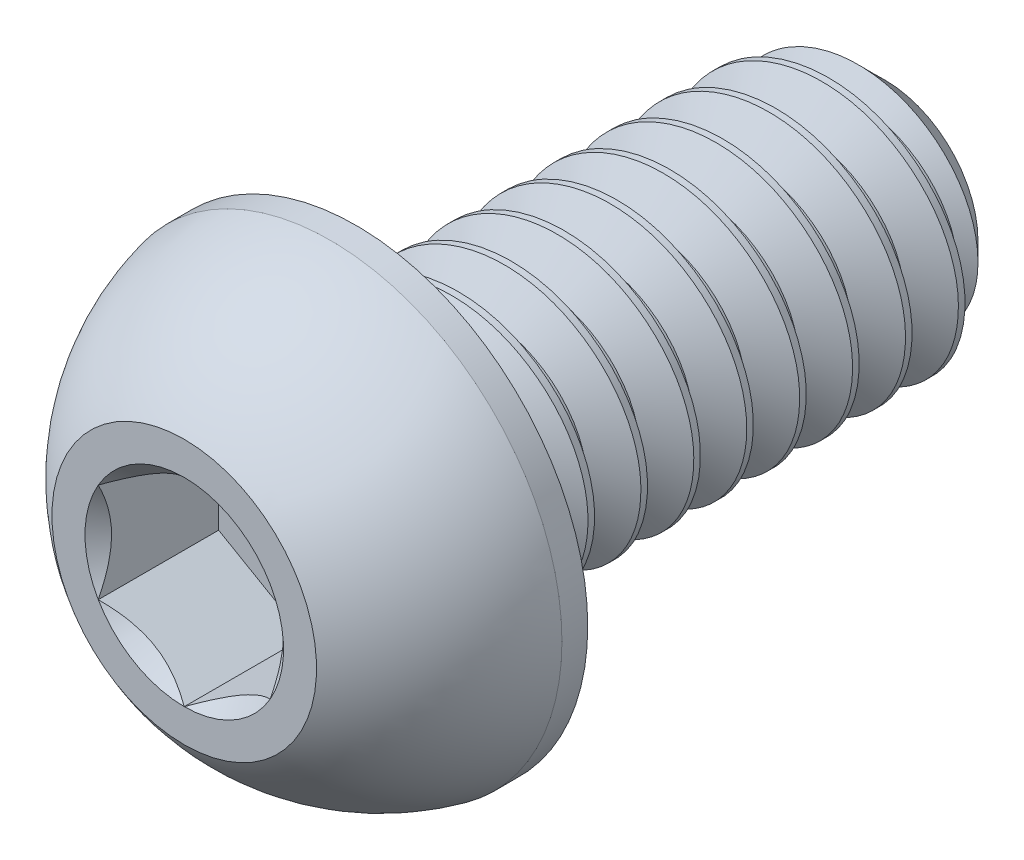
SolidWorks part; units mm, degrees
ref_plane "Front" through (0, 0, 0) normal (0, 0, 1) x (1, 0, 0)
ref_plane "Top" through (0, 0, 0) normal (0, 1, 0) x (1, 0, 0)
ref_plane "Right" through (0, 0, 0) normal (1, 0, 0) x (0, 0, -1)
sketch "Sketch1" plane through (0, 0, 0) normal (1, 0, 0) x (0, 0, -1)
  line L2 (1.3, 1) -> (5.3, 1)
  line L3 (5.3, 1) -> (5.3, 0)
  line L4 (5.3, 0) -> (1.3, 0)
  line L6 (1.105, 1.75) -> (1.3, 1.75) construction
  line L7 (5.3, 1) -> (5.3, -1) construction
  line L8 (0, 0) -> (1.3, 0) construction
  line L9 (1.3, 1.75) -> (1.3, -1.75) construction
  line L11 (1.3, 1) -> (1.3, 0)
  line L13 (0, 0.65) -> (0, -0.65) construction
  line L14 (0, 0.65) -> (0, 1) construction
  arc A3 (0, 1) -> (1.105, 1.75) centre (1.4858, 0) cw construction
  dimension "D1" = 0.195
revolve "Revolve1" add sketch "Sketch1" angle 360 mid plane about L4
sketch "Sketch3" plane through (0, 0, -5.3) normal (0, 0, -1) x (-1, 0, 0)
  circle A0 centre (0, 0) radius 1
curve "Helix/Spiral1" pitch 0.4 height 4.4 radius 1 centre (0, 0, -5.3) axis (0, 0, 1) start towards (1, 0, 0)
sketch "Sketch2" plane through (0, 0, 0) normal (1, 0, 0) x (0, 0, -1)
  line L0 (5.2, 1) -> (5.55, 1) construction
  line L1 (5.55, 1) -> (5.375, 0.6969) construction
  line L2 (5.375, 0.6969) -> (5.2, 1) construction
  line L3 (5.275, 0.8701) -> (5.475, 0.8701) construction
  line L4 (5.35, 0.7402) -> (5.4, 0.7402) construction
  line L5 (5.375, 0.7402) -> (5.375, 1) construction
  line L6 (5.2, 1) -> (5.55, 1)
  line L7 (5.55, 1) -> (5.4, 0.7402)
  line L8 (5.4, 0.7402) -> (5.35, 0.7402)
  line L9 (5.35, 0.7402) -> (5.2, 1)
  point P9 (5.375, 0.8701)
  dimension "D1" = 0.2
  dimension "D2" = 0.05
chamfer "Chamfer1" distance 0.3 angle 45 1 edges at (0, 1, -5.3)
sweep "Cut-Sweep1" cut profiles "Sketch2" path "Helix/Spiral1" align with end faces yes
sketch "Sketch7" plane through (0, 0, 0) normal (1, 0, 0) x (0, 0, -1)
  line L6 (1.105, 1.75) -> (1.3, 1.75) construction
  line L8 (0, 0) -> (1.3, 0) construction
  line L11 (1.3, 1.75) -> (1.3, -1.75) construction
  line L12 (1.105, 1.75) -> (1.3, 1.75)
  line L13 (0, 0) -> (1.3, 0)
  line L14 (0, 0.65) -> (0, -0.65) construction
  line L15 (1.3, 1.75) -> (1.3, 0)
  line L16 (0, 1) -> (0, 0)
  arc A2 (1.105, 1.75) -> (0, 1) centre (1.4858, 0) ccw construction
  arc A3 (1.105, 1.75) -> (0, 1) centre (1.4858, 0) ccw
revolve "Revolve2" add sketch "Sketch7" angle 360 mid plane about L13
sketch "Sketch5" plane through (0, 0, 0) normal (0, 0, 1) x (1, 0, 0)
  line L1 (0.65, -0.3753) -> (0.65, 0.3753)
  line L2 (0.65, 0.3753) -> (0, 0.7506)
  line L3 (0, 0.7506) -> (-0.65, 0.3753)
  line L4 (-0.65, 0.3753) -> (-0.65, -0.3753)
  line L5 (-0.65, -0.3753) -> (0, -0.7506)
  line L6 (0, -0.7506) -> (0.65, -0.3753)
  circle A0 centre (0, 0) radius 0.65 construction
extrude "Cut-Extrude2" cut sketch "Sketch5" against normal blind 0.91
sketch "Sketch6" plane through (0, 0, 0) normal (0, 0, 1) x (1, 0, 0)
  circle A0 centre (0, 0) radius 0.7506
extrude "Cut-Extrude3" cut sketch "Sketch6" against normal blind 0.91 draft 45
sketch "Sketch9" [suppressed] plane through (0, 0, -5.0546) normal (0, 0, 1) x (1, 0, 0)
  circle A2 centre (0, 0) radius 4.7625
extrude "Boss-Extrude2" [suppressed] add sketch "Sketch9" against normal offset from surface (6.35 mm away) 31.75 up to face at (0, 0.7, -5.3)
sketch "Sketch10" plane through (0, 0, 0) normal (1, 0, 0) x (0, 0, -1)
  line L0 (5.3, 1) -> (5.3, -1) construction
  point P0 (4.7, -1)
  dimension "D1" = 0.6
equation "\"D3@Helix/Spiral1\"=\"Lg@Sketch1\" + (\"D4@Helix/Spiral1\")"
equation "\"D1@Chamfer1\" = \"D4@Helix/Spiral1\" * .75"
equation "\"D1@Cut-Extrude2\" = \"Head Ht@Sketch1\" * .7"
equation "\"D1@Sketch1\" = \"Head Ht@Sketch1\" * .15"
equation "\"D1@Sketch10\" = \"D4@Helix/Spiral1\" * 1.5"
equation "\"D1@Cut-Extrude3\" = \"D1@Cut-Extrude2\""
equation "\"D1@Sketch2\"=\"D4@Helix/Spiral1\"*.5"
equation "\"D2@Sketch2\"=\"D4@Helix/Spiral1\"*.125"
